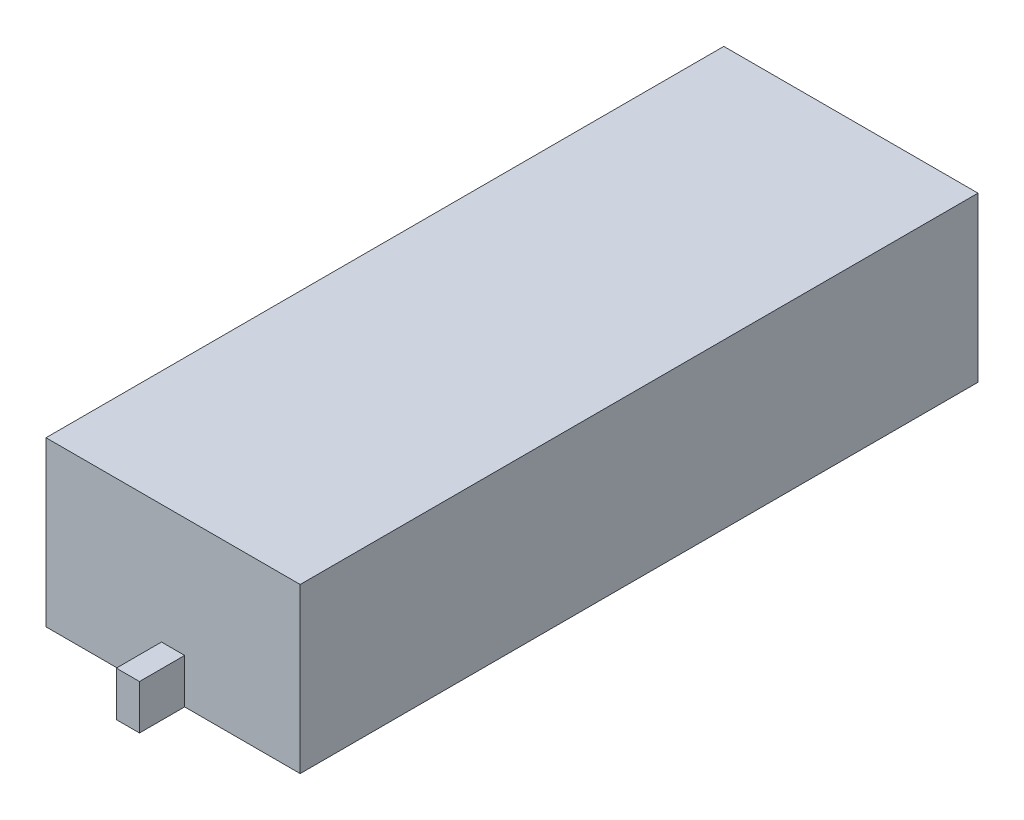
SolidWorks part; units mm, degrees
ref_plane "Front Plane" through (0, 0, 0) normal (0, 0, 1) x (1, 0, 0)
ref_plane "Top Plane" through (0, 0, 0) normal (0, 1, 0) x (1, 0, 0)
ref_plane "Right Plane" through (0, 0, 0) normal (1, 0, 0) x (0, 0, -1)
sketch "SK_Pack" plane through (0, 0, 0) normal (0, 1, 0) x (1, 0, 0)
  line L1 (-45, 120) -> (45, 120)
  line L2 (-45, 120) -> (-45, -120)
  line L3 (-45, -120) -> (45, -120)
  line L4 (45, 120) -> (45, -120)
  dimension "D1" = 240
  dimension "D2" = 90
  dimension "D3" = 120
  dimension "D4" = 45
extrude "EX_Pack" add sketch "SK_Pack" along normal blind 58
sketch "SK_XT60" plane through (0, 0, 0) normal (0, 1, 0) x (1, 0, 0)
  line L1 (-4.1, -120) -> (4.1, -120)
  line L2 (-4.1, -120) -> (-4.1, -136)
  line L3 (-4.1, -136) -> (4.1, -136)
  line L4 (4.1, -120) -> (4.1, -136)
  dimension "D3" = 120
  dimension "D1" = 16
  dimension "D2" = 8.2
  dimension "D4" = 4.1
extrude "EX_XT60" add sketch "SK_XT60" along normal blind 15.8
ref_axis "AX_X" through (0, 0, -132.8) along (0, 0, 1)
ref_axis "AX_Y" through (49.5, 0, 0) along (-1, 0, 0)
ref_axis "AX_Z" through (0, 60.9, 0) along (0, -1, 0)
equation "\"BODY_L\"= 420"
equation "\"BODY_W\"= 340"
equation "\"FLOOR_Z\"= 35"
equation "\"DECK_Z\"= 180"
equation "\"DECK_T\"= 2"
equation "\"GRID\"= 20"
equation "\"PROFILE\"= 20"
equation "\"SM_T\"= 1.5"
equation "\"PAN_T\"= 1.5"
equation "\"PAN_TOP\"= \"FLOOR_Z\" + \"PAN_T\""
equation "\"RAIL_Y\"= 140"
equation "\"RAIL_X\"= \"BODY_L\" / 2 - \"PROFILE\" / 2 - 2"
equation "\"BOTRING_Z\"= \"PAN_TOP\" + \"PROFILE\" / 2"
equation "\"TOPRING_Z\"= \"DECK_Z\" - \"DECK_T\" - \"PROFILE\" / 2"
equation "\"DRAWER_Z\"= 93"
equation "\"MIDX_Z\"= \"DRAWER_Z\" - \"SM_T\" - \"PROFILE\" / 2"
equation "\"SKIN_Y\"= \"RAIL_Y\" + \"PROFILE\" / 2"
equation "\"SKIN_T\"= 2"
equation "\"WHEEL_D\"= 144"
equation "\"WHEEL_W\"= 52"
equation "\"TRACK\"= 365"
equation "\"AXLE_Z\"= \"WHEEL_D\" / 2"
equation "\"WHEEL_WEB_OFF\"= 6"
equation "\"HUB_T\"= 8"
equation "\"BUSHING_L\"= 6"
equation "\"HUB_GAP\"= 1"
equation "\"MOTOR_UP\"= 7"
equation "\"MOTOR_FACE_Y\"= \"TRACK\" / 2 + \"WHEEL_WEB_OFF\" - (\"BUSHING_L\" + \"HUB_GAP\" + \"HUB_T\")"
equation "\"MOTOR_AXIS_Z\"= \"AXLE_Z\" + \"MOTOR_UP\""
equation "\"CASTER_D\"= 50"
equation "\"CASTER_X\"= 150"
equation "\"CASTER_H\"= 68"
equation "\"POST_X\"= -40"
equation "\"POST_DY\"= 120"
equation "\"POST_SIZE\"= 20"
equation "\"POST_TOP\"= 400"
equation "\"BRACE_Z\"= 335"
equation "\"STRUT_X0\"= -140"
equation "\"HEAD_X0\"= -110"
equation "\"HEAD_X1\"= 12"
equation "\"BEZEL_T\"= 3"
equation "\"WEDGE_MID\"= 7.7"
equation "\"OAK_D\"= 22.9"
equation "\"HEAD_W\"= 210"
equation "\"HEAD_Z0\"= \"POST_TOP\""
equation "\"HEAD_TOP\"= 525"
equation "\"HEAD_TOP_X\"= -20"
equation "\"SCREEN_ANG\"= 35"
equation "\"LENS_X\"= 45.6"
equation "\"LENS_Z\"= 450"
equation "\"OAK_TILT\"= 5"
equation "\"OAK_VFOV_DEPTH\"= 79.5"
equation "\"OAK_VFOV_RGB\"= 72"
equation "\"LIDAR_X\"= 110"
equation "\"SCAN_Z\"= 260"
equation "\"STRUT_Z\"= \"SCAN_Z\" - 20"
equation "\"LIDAR_SCAN_H\"= 27.2"
equation "\"LIDAR_MOUNT_Z\"= \"SCAN_Z\" - \"LIDAR_SCAN_H\""
equation "\"ESTOP_X\"= -172.5"
equation "\"ESTOP_Y\"= -127.5"
equation "\"ESTOP_TOP\"= 225"
equation "\"BUMPER_T\"= 15"
equation "\"BUMPER_Z0\"= 40"
equation "\"BUMPER_Z1\"= 130"
equation "\"CLIFF_X\"= 218"
equation "\"CLIFF_Y\"= 105"
equation "\"CLIFF_Z\"= 72"
equation "\"CLIFF_ANG\"= 50"
equation "\"CONTACT_X\"= 216"
equation "\"CONTACT_Y\"= 64"
equation "\"CONTACT_Z\"= 30"
equation "\"DOCK_TAG_DIST\"= 250"
equation "\"DOCK_TAG_SIZE\"= 80"
equation "\"DOCK_TAG_Z\"= 400"
equation "\"BAT_L\"= 240"
equation "\"BAT_W\"= 90"
equation "\"BAT_H\"= 58"
equation "\"BAT_Z\"= \"DRAWER_Z\" + \"SM_T\""
equation "\"BAT_X\"= 0"
equation "\"PCB_L\"= 95"
equation "\"PCB_W\"= 120"
equation "\"PCB_H\"= 40"
equation "\"PCB_X\"= 62.5"
equation "\"DRV_X\"= 85"
equation "\"DRV_Y\"= 100"
equation "\"DRV_S\"= 50"
equation "\"COMPUTE_X\"= -65"
equation "\"COMPUTE_L\"= 90"
equation "\"COMPUTE_W\"= 160"
equation "\"D1@SK_Pack\" = \"BAT_L\""
equation "\"D2@SK_Pack\" = \"BAT_W\""
equation "\"D3@SK_Pack\" = (\"BAT_L\") / 2"
equation "\"D4@SK_Pack\" = (\"BAT_W\") / 2"
equation "\"D1@EX_Pack\" = \"BAT_H\""
equation "\"D3@SK_XT60\" = \"BAT_L\" / 2"
